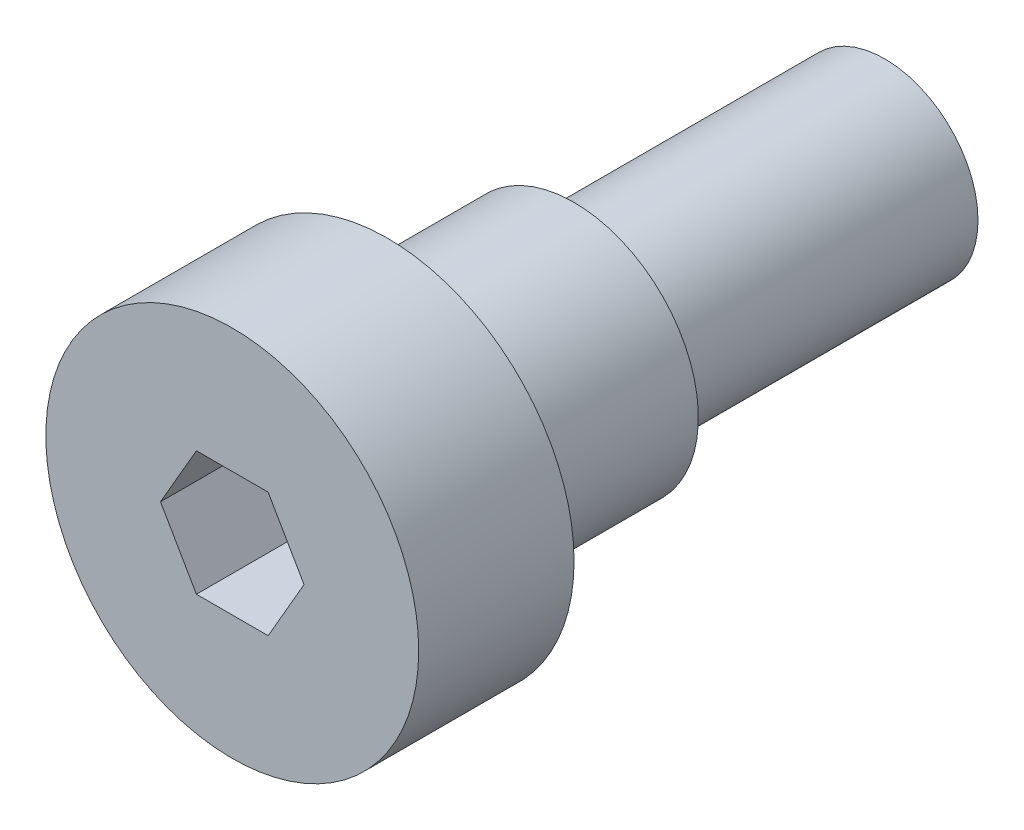
SolidWorks part; units mm, degrees
material "Alloy Steel"
ref_plane "Front" through (0, 0, 0) normal (0, 0, 1) x (1, 0, 0)
ref_plane "Top" through (0, 0, 0) normal (0, 1, 0) x (1, 0, 0)
ref_plane "Right" through (0, 0, 0) normal (1, 0, 0) x (0, 0, -1)
sketch "Sketch1" plane through (0, 0, 0) normal (0, 0, 1) x (1, 0, 0)
  circle A0 centre (0, 0) radius 4.7625
  dimension "D1" = 9.525
extrude "Boss-Extrude1" add sketch "Sketch1" along normal blind 15.875
cosmetic thread "Cosmetic Thread1" parameters "D2"=8.2652
sketch "Sketch2" plane through (0, 0, 15.875) normal (0, 0, 1) x (1, 0, 0)
  circle A0 centre (0, 0) radius 6.35
  dimension "D1" = 12.7
extrude "Boss-Extrude2" add sketch "Sketch2" along normal blind 9.525
sketch "Sketch3" plane through (0, 0, 25.4) normal (0, 0, 1) x (1, 0, 0)
  circle A0 centre (0, 0) radius 9.525
  dimension "D1" = 19.05
extrude "Boss-Extrude3" add sketch "Sketch3" along normal blind 7.9375
sketch "Sketch4" plane through (0, 0, 33.3375) normal (0, 0, 1) x (1, 0, 0)
  line L1 (-3.6662, 0) -> (-1.8331, -3.175)
  line L2 (-1.8331, -3.175) -> (1.8331, -3.175)
  line L3 (1.8331, -3.175) -> (3.6662, 0)
  line L4 (3.6662, 0) -> (1.8331, 3.175)
  line L5 (1.8331, 3.175) -> (-1.8331, 3.175)
  line L6 (-1.8331, 3.175) -> (-3.6662, 0)
  circle A1 centre (0, 0) radius 3.175 construction
extrude "Cut-Extrude1" cut sketch "Sketch4" against normal blind 6.35
